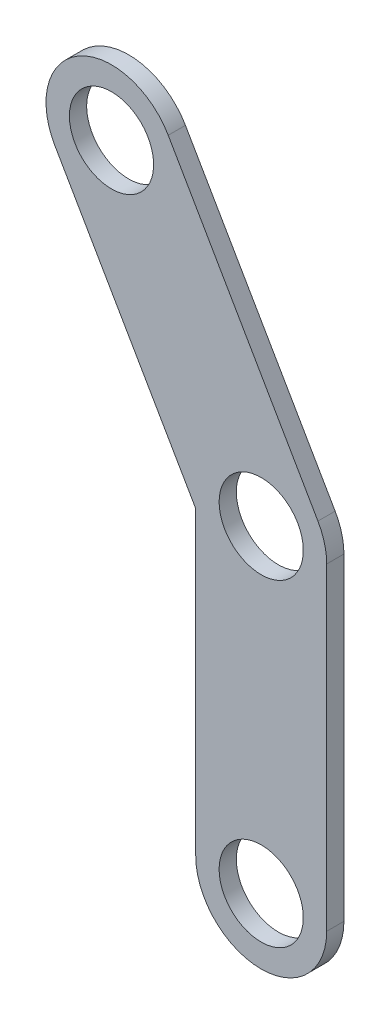
SolidWorks part; units mm, degrees
ref_plane "Front Plane" through (0, 0, 0) normal (0, 0, 1) x (1, 0, 0)
ref_plane "Top Plane" through (0, 0, 0) normal (0, 1, 0) x (1, 0, 0)
ref_plane "Right Plane" through (0, 0, 0) normal (1, 0, 0) x (0, 0, -1)
ref_plane "Plane1" through (0, 0, 0) normal (0, 0, -1) x (-1, 0, 0)
sketch "Sketch1" plane through (0, 0, 0) normal (0, 0, -1) x (-1, 0, 0)
  line L30 (51.5636, -4.2866) -> (51.5636, 103.6634) construction
  line L31 (51.5636, 103.6634) -> (102.3636, 191.6516) construction
  line L32 (29.3386, -4.2866) -> (29.3386, 103.6634)
  line L33 (83.1162, 202.7641) -> (32.3162, 114.7759)
  line L34 (121.611, 180.5391) -> (70.811, 92.5509)
  line L35 (73.7886, -4.2866) -> (73.7886, 103.6634)
  line L36 (51.5636, 103.6634) -> (51.5636, -4.2866) construction
  circle A1 centre (102.3636, 191.6516) radius 14.2875
  circle A7 centre (51.5636, -4.2866) radius 22.225
  circle A8 centre (51.5636, 103.6634) radius 22.225
  circle A9 centre (102.3636, 191.6516) radius 22.225
  circle A10 centre (51.5636, 103.6634) radius 14.2875
  circle A11 centre (51.5636, -4.2866) radius 14.2875
  dimension "D1" = 28.575
  dimension "D2" = 28.575
  dimension "D3" = 107.95
  dimension "D4" = 210
  dimension "D7" = 44.45
  dimension "D8" = 44.45
  dimension "D9" = 44.45
  dimension "D5" = 107.95
  dimension "D6" = 101.6
  dimension "D10" = 0
extrude "Boss-Extrude1" add sketch "Sketch1" against normal blind 5.842 contours A8 L32 A7 L35 L34 | A9 L33 A8 L35 L34 | A8 A10 | A7 A11 | A8 L34 L35 | A9 A1 region at (-51.5433, 49.6433, 0) region at (-51.5636, 17.3098, 0) region at (-30.7031, 109.253, 0) region at (-76.9675, 147.7086, 0) region at (-73.186, 97.8697, 0) region at (-107.9531, 212.5121, 0)
